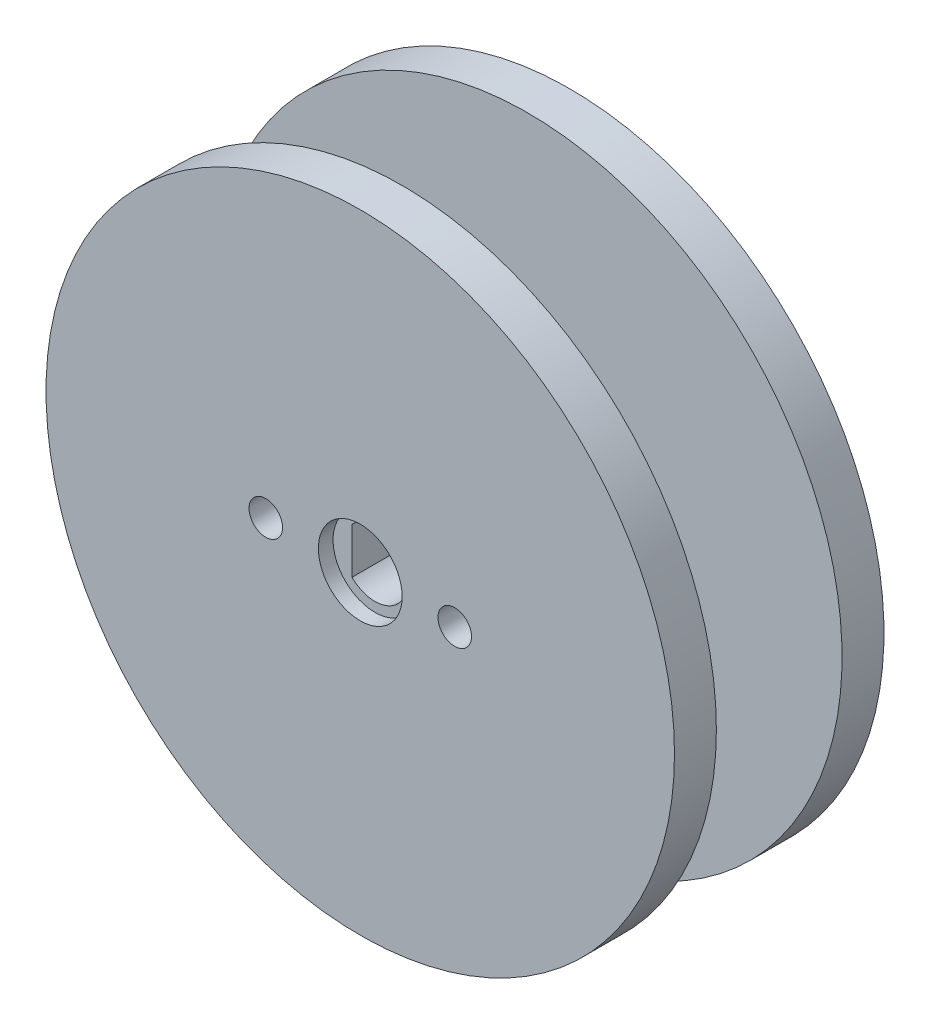
SolidWorks part; units mm, degrees
ref_plane "Front Plane" through (0, 0, 0) normal (0, 0, 1) x (1, 0, 0)
ref_plane "Top Plane" through (0, 0, 0) normal (0, 1, 0) x (1, 0, 0)
ref_plane "Right Plane" through (0, 0, 0) normal (1, 0, 0) x (0, 0, -1)
sketch "Sketch1" plane through (0, 0, 0) normal (0, 0, 1) x (1, 0, 0)
  circle A0 centre (0, 0) radius 2.5
  dimension "D1" = 5
extrude "Boss-Extrude1" add sketch "Sketch1" along normal blind 6 contours A0
sketch "Sketch2" plane through (0, 0, 0) normal (0, 0, -1) x (-1, 0, 0)
  circle A0 centre (0, 0) radius 15
  dimension "D1" = 30
extrude "Boss-Extrude2" add sketch "Sketch2" along normal blind 2
sketch "Sketch3" plane through (0, 0, 6) normal (0, 0, 1) x (1, 0, 0)
  circle A0 centre (0, 0) radius 15
  dimension "D1" = 30
extrude "Boss-Extrude3" add sketch "Sketch3" along normal blind 2 contours A0
fillet "Fillet9" radius 3 1 edges at (2.5, 0, 0) type face fillet first side face at (2.5, 0, 0) second side face at (2.5, 0, 6)
fillet "Fillet10" radius 3 1 edges at (2.5, 0, 6) type face fillet first side face at (2.5, 0, 6) second side face at (-2.5, 0, 3)
sketch "Sketch4" plane through (0, 0, -2) normal (0, 0, -1) x (-1, 0, 0)
  line L1 (1.0953, 1.0967) -> (1.0953, -1.0967)
  arc A0 (1.0953, 1.0967) -> (1.0953, -1.0967) centre (0, 0) ccw
  dimension "D1" = 3.1
extrude "Cut-Extrude1" cut sketch "Sketch4" against normal blind 10
sketch "Sketch5" plane through (0, 0, 8) normal (0, 0, 1) x (1, 0, 0)
  circle A0 centre (0, 0) radius 1.9994
  dimension "D1" = 3.9987
extrude "Cut-Extrude2" cut sketch "Sketch5" against normal blind 0.7
sketch "Sketch7" plane through (0, 0, 8) normal (0, 0, 1) x (1, 0, 0)
  line L0 (0, 0) -> (4.5094, 0)
  line L1 (0, 0) -> (-4.5094, 0)
  circle A0 centre (0, 0) radius 1.9994 construction
  circle A1 centre (0, 0) radius 1.9994 construction
  circle A2 centre (4.5094, 0) radius 0.8
  circle A3 centre (-4.5094, 0) radius 0.8
  dimension "D1" = 4.5094
  dimension "1.6" = 1.6
  dimension "D2" = 1.6
  dimension "D3" = 4.5094
extrude "Cut-Extrude6" cut sketch "Sketch7" against normal blind 3 contours A2 | A3
sketch "Sketch8" plane through (0, 0, -2) normal (0, 0, -1) x (-1, 0, 0)
  line L0 (0, 0) -> (4.5, 0)
  line L1 (0, 0) -> (-4.5, 0)
  circle A1 centre (-4.5, 0) radius 0.8
  circle A2 centre (4.5, 0) radius 0.8
  dimension "D1" = 1.6
  dimension "1.6mm" = 1.6
extrude "Cut-Extrude7" cut sketch "Sketch8" against normal blind 5 contours A1 | A2
